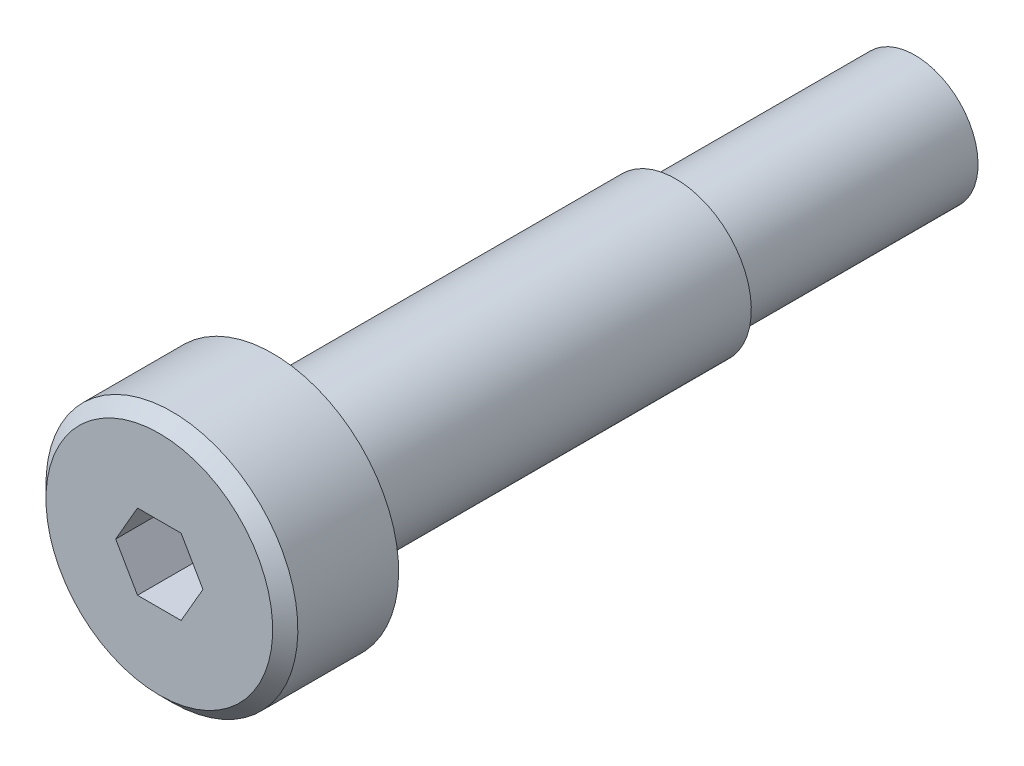
SolidWorks part; units mm, degrees
material "Alloy Steel"
ref_plane "Front Plane" through (0, 0, 0) normal (0, 0, 1) x (1, 0, 0)
ref_plane "Top Plane" through (0, 0, 0) normal (0, 1, 0) x (1, 0, 0)
ref_plane "Right Plane" through (0, 0, 0) normal (1, 0, 0) x (0, 0, -1)
ref_axis "Axis1" through (0, 0, -52.8182) along (0, 0, 1)
ref_axis "Axis2" through (0, -15.5981, 0) along (0, 1, 0)
ref_axis "Axis3" through (-12.2581, 0, 0) along (1, 0, 0)
sketch "Sketch1" plane through (0, 0, 0) normal (1, 0, 0) x (0, 0, -1)
  line L0 (-16, 3) -> (-16, 5)
  line L1 (-16, 3) -> (0, 3)
  line L2 (0, 3) -> (0, 2.5)
  line L3 (0, 2.5) -> (9.5, 2.5)
  line L4 (9.5, 2.5) -> (9.5, 0)
  line L5 (9.5, 0) -> (-20.5, 0)
  line L6 (-5.5849, 0) -> (13.8966, 0) construction
  line L7 (-16, 5) -> (-20, 5)
  line L8 (-20.5, 4.5) -> (-20.5, 0)
  line L9 (-20, 5) -> (-20.5, 4.5)
  point P11 (-20.5, 5)
  dimension "D1" = 5
  dimension "D2" = 6
  dimension "D3" = 9.5
  dimension "LENGTH" = 16
  dimension "D4" = 4.5
  dimension "D5" = 10
revolve "Revolve1" add sketch "Sketch1" angle 360 about L6
cosmetic thread "Cosmetic Thread1" parameters "D2"=4.11
sketch "Sketch2" plane through (0, 0, 20.5) normal (0, 0, 1) x (1, 0, 0)
  line L1 (0.866, -1.5) -> (1.7321, 0)
  line L2 (1.7321, 0) -> (0.866, 1.5)
  line L3 (0.866, 1.5) -> (-0.866, 1.5)
  line L4 (-0.866, 1.5) -> (-1.7321, 0)
  line L5 (-1.7321, 0) -> (-0.866, -1.5)
  line L6 (-0.866, -1.5) -> (0.866, -1.5)
  circle A0 centre (0, 0) radius 1.5 construction
  dimension "D1" = 3
extrude "Cut-Extrude1" cut sketch "Sketch2" against normal blind 2.7
